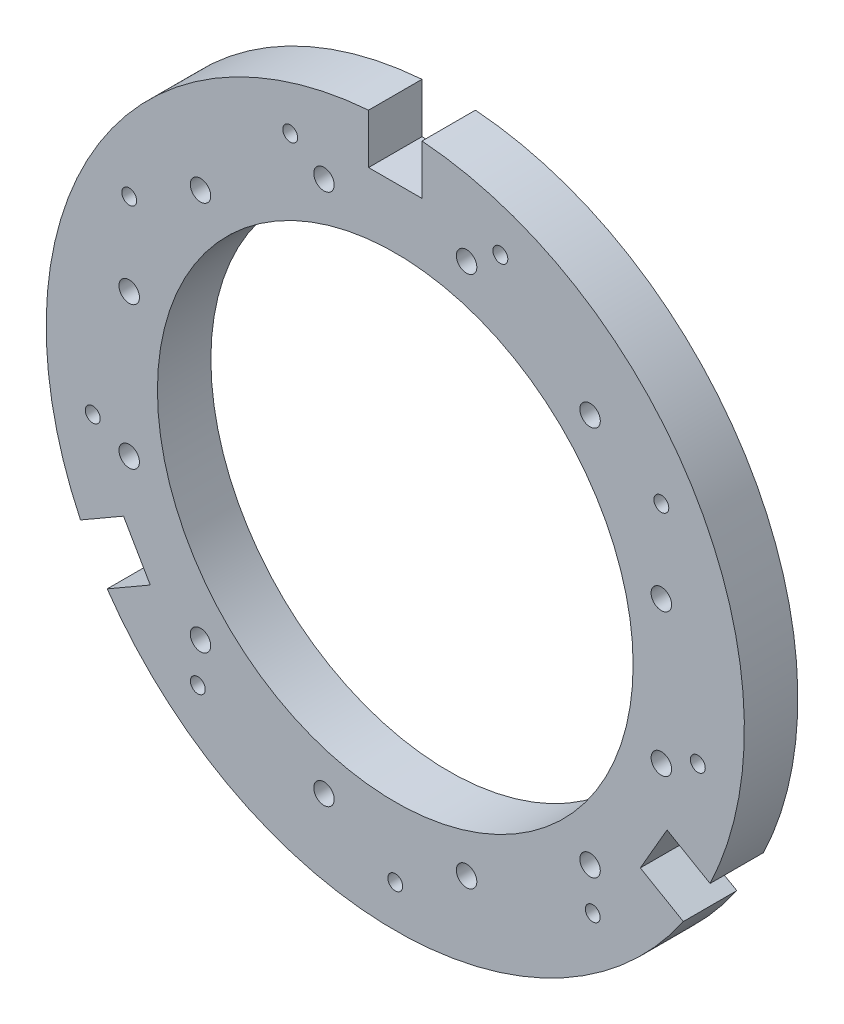
SolidWorks part; units mm, degrees
material "Teck"
ref_plane "Plan de face" through (0, 0, 0) normal (0, 0, 1) x (1, 0, 0)
ref_plane "Plan de dessus" through (0, 0, 0) normal (0, 1, 0) x (1, 0, 0)
ref_plane "Plan de droite" through (0, 0, 0) normal (1, 0, 0) x (0, 0, -1)
sketch "Esquisse1" plane through (0, 0, 0) normal (0, 0, 1) x (1, 0, 0)
  line L0 (5.741, 64.1) -> (5.741, 50.7765) construction
  line L1 (52.6417, -37.0219) -> (61.8908, -42.3618)
  line L2 (0, 51.1) -> (0, 0) construction
  line L3 (58.3827, -27.0781) -> (67.6318, -32.4181)
  line L4 (0, 51.1) -> (5.741, 51.1) construction
  line L5 (5.741, 64.1) -> (5.741, 74.7799)
  line L6 (5.741, 64.1) -> (-5.741, 64.1)
  line L7 (-5.741, 64.1) -> (-5.741, 74.7799)
  line L8 (52.6417, -37.0219) -> (58.3827, -27.0781)
  line L9 (-58.3827, -27.0781) -> (-67.6318, -32.4181)
  line L10 (-52.6417, -37.0219) -> (-61.8908, -42.3618)
  line L11 (-58.3827, -27.0781) -> (-52.6417, -37.0219)
  arc A0 (5.741, 74.7799) -> (67.6318, -32.4181) centre (0, 0) cw
  circle A1 centre (0, 0) radius 75 construction
  circle A2 centre (0, 0) radius 51.1
  arc A4 (-5.741, 74.7799) -> (-67.6318, -32.4181) centre (0, 0) ccw
  arc A5 (-61.8908, -42.3618) -> (61.8908, -42.3618) centre (0, 0) ccw
  point P22 (0, 0)
  dimension "D4" = 150
  dimension "D6" = 102.2
  dimension "D2" = 5.741
  dimension "D5" = 11.482
  dimension "D7" = 13
  dimension "D1" = 3
extrude "Boss.-Extru.1" add sketch "Esquisse1" along normal blind 11.482 contours L10 A5 L1 L8 L3 A0 L5 L6 L7 A4 L9 L11 A2
sketch "Sketch2" plane through (0, 0, 11.482) normal (0, 0, 1) x (1, 0, 0)
  line L0 (0, 0) -> (0, 96.9743) construction
  line L1 (0, 0) -> (22.5733, 62.0197) construction
  line L2 (22.5733, 62.0197) -> (38.7609, 106.4946) construction
  circle A0 centre (22.5733, 62.0197) radius 1.6
  dimension "D2" = 3.2
  dimension "D1" = 66
  dimension "D5" = 20
extrude "Cut-Extrude1" cut sketch "Sketch2" against normal through all
ref_axis "Axis1" through (0, 0, -0.5741) along (0, 0, 1)
pattern_circular "CirPattern1" count 9 over 360 about axis through (0, 0, -0.5741) along (0, 0, 1) of "Cut-Extrude1" reverse direction yes
sketch "Sketch3" plane through (0, 0, 0) normal (0, 0, 1) x (1, 0, 0)
  line L0 (0, 0) -> (0, 40) construction
  line L1 (0, 0) -> (15.3169, 57.1635) construction
  circle A0 centre (15.3169, 57.1635) radius 2.2
  dimension "D4" = 4.4
  dimension "D1" = 40
  dimension "D2" = 15
  dimension "D3" = 59.18
extrude "Cut-Extrude2" cut sketch "Sketch3" against normal mid plane 50
pattern_circular "CirPattern2" count 12 over 360 about axis through (0, 0, -0.5741) along (0, 0, 1) of "Cut-Extrude2"
equation "\"d_i_tube\"= 150mm'Inner Rocket Body Composite Tube Diameter"
equation "\"t_tube\"= 1.182mm'Thickness of Rocket Body Composite Tube"
equation "\"l_upper_body_tube\"= 1190mm'Upper Rocket Body Composite Tube length"
equation "\"l_lower_body_tube\"= 896mm'Lower Rocket Body Composite Tube Length"
equation "\"d_a_NC\"= 154mm'Outer Diameter of Nosecone base"
equation "\"d_i_phenolic_tube\"= 152.3mm'Inner Phenolic Tube Diameter"
equation "\"t_phenolic_tube\"= 2mm'Thickness of Phenolic Body Tube"
equation "\"l_fin_cut\"= 220mm'Length of fin on Motor Retainer"
equation "\"t_SW-Panel\"= 11.482mm'Thickness of Sandwich-Panel"
equation "\"l_motor_tube\"=650mm'Length of phenolic motor tube"
equation "\"d_i_motor_tube\"=99.06mm'Inner diameter of phenolic motor tube"
equation "\"t_motor_tube\"=1.58mm'Thicknes of phenolic motor tube"
equation "\"D4@Esquisse1\"=\"d_i_tube\""
equation "\"D6@Esquisse1\"=102.2"
equation "\"D2@Esquisse1\"=\"t_SW-Panel\"/2"
equation "\"D5@Esquisse1\"=\"t_SW-Panel\""
equation "\"D1@Boss.-Extru.1\"=\"t_SW-Panel\""
